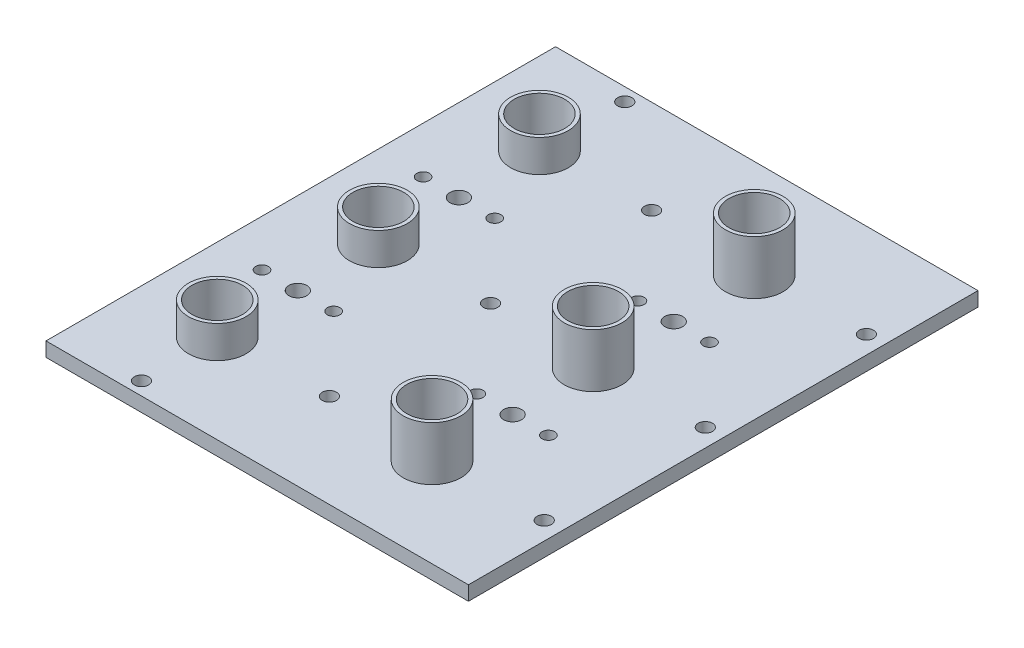
SolidWorks part; units mm, degrees
ref_plane "Płaszczyzna przednia" through (0, 0, 0) normal (0, 0, 1) x (1, 0, 0)
ref_plane "Płaszczyzna górna" through (0, 0, 0) normal (0, 1, 0) x (1, 0, 0)
ref_plane "Płaszczyzna prawa" through (0, 0, 0) normal (1, 0, 0) x (0, 0, -1)
sketch "Sketch1" plane through (0, 0, 0) normal (0, 1, 0) x (1, 0, 0)
  line L0 (0, 45) -> (60, 45) construction
  line L1 (0, 45) -> (0, -11.0512) construction
  line L2 (0, 0) -> (60, 0) construction
  line L3 (0, -45) -> (60, -45) construction
  line L4 (-53, 71.1698) -> (-53, -71.1698)
  line L5 (-30, 67.5) -> (-30, -67.5) construction
  line L6 (65, 71.1698) -> (65, -71.1698)
  line L7 (65, -71.1698) -> (-53, -71.1698)
  line L8 (-53, 71.1698) -> (65, 71.1698)
  circle A0 centre (0, 45) radius 2
  circle A1 centre (60, 45) radius 2
  circle A2 centre (0, 0) radius 2
  circle A3 centre (60, 0) radius 2
  circle A4 centre (0, -45) radius 2
  circle A5 centre (60, -45) radius 2
  circle A6 centre (-30, 67.5) radius 2
  circle A7 centre (-30, -67.5) radius 2
  point P23 (-53, 0)
  point P26 (-30, 0)
  dimension "D1" = 4
  dimension "D2" = 4
  dimension "D5" = 45
  dimension "D6" = 4
  dimension "D7" = 135
  dimension "D3" = 60
  dimension "D4" = 3
  dimension "D8" = 53
  dimension "D9" = 23
  dimension "D10" = 5
extrude "Boss-Extrude1" add sketch "Sketch1" along normal blind 4
sketch "Sketch2" plane through (0, 4, 0) normal (0, 1, 0) x (1, 0, 0)
  line L1 (-35, 48.6698) -> (-25, 48.6698) construction
  line L2 (-35, 48.6698) -> (-35, 38.6698) construction
  line L3 (-35, 38.6698) -> (-25, 38.6698) construction
  line L4 (-25, 48.6698) -> (-25, 38.6698) construction
  line L5 (-25, 38.6698) -> (-35, 48.6698) construction
  line L6 (-53, 71.1698) -> (-53, -71.1698) construction
  circle A0 centre (-30, 43.6698) radius 7.0711
  circle A1 centre (-30, 43.6698) radius 8.0711
  circle A2 centre (-30, -1.3302) radius 8.0711
  circle A3 centre (-30, -1.3302) radius 7.0711
  circle A4 centre (-30, -46.3302) radius 8.0711
  circle A5 centre (-30, -46.3302) radius 7.0711
  circle A6 centre (30, 43.6698) radius 8.0711
  circle A7 centre (30, 43.6698) radius 7.0711
  circle A8 centre (30, -1.3302) radius 8.0711
  circle A9 centre (30, -1.3302) radius 7.0711
  circle A10 centre (30, -46.3302) radius 8.0711
  circle A11 centre (30, -46.3302) radius 7.0711
  point P11 (-30, 43.6698)
  dimension "D5" = 1
  dimension "D1" = 10
  dimension "D2" = 10
  dimension "D3" = 3
  dimension "D4" = 18
  dimension "D6" = 2
extrude "Boss-Extrude2" add sketch "Sketch2" along normal blind 9 contours A1 A0 | A2 A3 | A4 A5 region at (-37.8428, 4, -43.6698) region at (-37.8428, 4, 1.3302) region at (-37.8428, 4, 46.3302)
extrude "Boss-Extrude3" add sketch "Sketch2<4>" along normal blind 15 contours A6 A7 | A8 A9 | A10 A11 region at (22.1572, 4, -43.6698) region at (22.1572, 4, 1.3302) region at (22.1572, 4, 46.3302)
sketch "Sketch2<4>" plane through (0, 4, 0) normal (0, 1, 0) x (1, 0, 0) same geometry as "Sketch2"
extrude "Cut-Extrude1" cut sketch "Sketch2<5>" against normal blind 52 contours A11 | A5 | A3 | A0 | A7 | A9 region at (-30, 4, -43.6698) region at (-30, 4, 1.3302) region at (-30, 4, 46.3302) region at (30, 4, -43.6698) region at (30, 4, 1.3302) region at (30, 4, 46.3302)
sketch "Sketch2<5>" plane through (0, 4, 0) normal (0, 1, 0) x (1, 0, 0) same geometry as "Sketch2"
sketch "Sketch4" plane through (0, 0, 0) normal (0, -1, 0) x (1, 0, 0)
  line L0 (30, 1.3302) -> (30, -43.6698) construction
  line L1 (30, -21.1698) -> (40, -21.1698) construction
  circle A0 centre (40, -21.1698) radius 1.75
  circle A1 centre (20, -21.1698) radius 1.75
  circle A2 centre (30, -21.1698) radius 2.5
  circle A4 centre (30, -43.6698) radius 7.0711 construction
  circle A5 centre (30, 1.3302) radius 7.0711 construction
  circle A6 centre (-40, -21.1698) radius 1.75
  circle A7 centre (-30, -21.1698) radius 2.5
  circle A8 centre (-20, -21.1698) radius 1.75
  circle A9 centre (-40, 23.8302) radius 1.75
  circle A10 centre (-30, 23.8302) radius 2.5
  circle A11 centre (-20, 23.8302) radius 1.75
  circle A12 centre (20, 23.8302) radius 1.75
  circle A13 centre (30, 23.8302) radius 2.5
  circle A14 centre (40, 23.8302) radius 1.75
  dimension "D1" = 3.5
  dimension "D2" = 10
  dimension "D3" = 5
  dimension "D4" = 2
  dimension "D5" = 2
extrude "Cut-Extrude2" cut sketch "Sketch4" against normal blind 52
